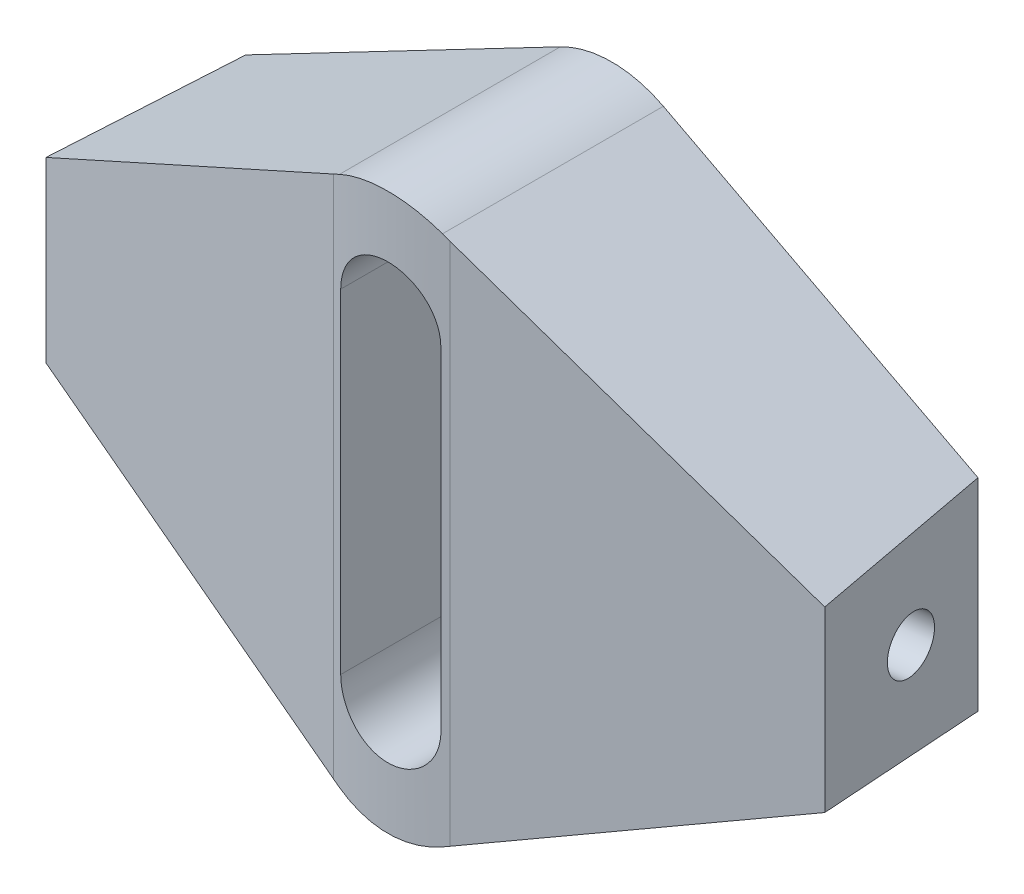
SolidWorks part; units mm, degrees
material "PVC hart"
ref_plane "Ebene vorne" through (0, 0, 0) normal (0, 0, 1) x (1, 0, 0)
ref_plane "Ebene oben" through (0, 0, 0) normal (0, 1, 0) x (1, 0, 0)
ref_plane "Ebene rechts" through (0, 0, 0) normal (1, 0, 0) x (0, 0, -1)
sketch "Skizze3" plane through (0, 0, 0) normal (0, 0, 1) x (1, 0, 0)
  line L0 (-17.5, 4) -> (-2.3149, 11.9318)
  line L1 (0, -7.5) -> (0, 7.5) construction
  line L2 (-2.25, -7.5) -> (-2.25, 7.5)
  line L3 (2.25, -7.5) -> (2.25, 7.5)
  line L4 (-17.5, 0) -> (17.5, 0) construction
  line L5 (-17.5, -4) -> (-2.3149, -11.9318)
  line L6 (0, 12.5) -> (0, -12.5) construction
  line L7 (17.5, -4) -> (2.3149, -11.9318)
  line L8 (-17.5, -4) -> (-17.5, 4)
  line L9 (17.5, 4) -> (2.3149, 11.9318)
  line L10 (17.5, -4) -> (17.5, 4)
  arc A0 (-2.25, -7.5) -> (2.25, -7.5) centre (0, -7.5) ccw
  arc A1 (2.25, 7.5) -> (-2.25, 7.5) centre (0, 7.5) ccw
  arc A2 (-2.3149, 11.9318) -> (2.3149, 11.9318) centre (0, 7.5) cw
  arc A3 (-2.3149, -11.9318) -> (2.3149, -11.9318) centre (0, -7.5) ccw
  point P4 (0, 0)
  point P15 (0, 0)
  dimension "D1" = 4.5
  dimension "D2" = 25
  dimension "D3" = 15
  dimension "D4" = 8
  dimension "D5" = 35
extrude "Aufsatz-Linear austragen3" add sketch "Skizze3" along normal blind 20 contours L2 A1 L3 | L8 | L2 | L3 | L10 | L3 A0 L2 region at (-9.7083, 7.5847, 0)
sketch "Skizze10" plane through (0, 0, 0) normal (0, 1, 0) x (1, 0, 0)
  line L0 (-16.4558, 0) -> (-17.5, -7.9316)
  line L1 (-17.5, 0) -> (-2.3149, 0) construction
  line L2 (-17.5, -20) -> (-17.5, 0) construction
  line L3 (-17.5, -7.9316) -> (-2.6105, -9.8918)
  line L5 (0, 0) -> (0, -20) construction
  line L6 (2.3149, 0) -> (-2.3149, 0) construction
  line L7 (-2.3149, -20) -> (2.3149, -20) construction
  line L8 (-16.4558, 0) -> (16.4558, 0)
  line L9 (16.4558, 0) -> (17.5, -7.9316)
  line L10 (17.5, -7.9316) -> (2.6105, -9.8918)
  arc A0 (-2.6105, -9.8918) -> (2.6105, -9.8918) centre (0, 9.9371) ccw
  dimension "D3" = 20
  dimension "D1" = 8
  dimension "D2" = 165
extrude "Schnitt-Linear austragen9" cut sketch "Skizze10" against normal through all and the other way through all flip side to cut
sketch "Skizze7" plane through (-17.1964, 0, 5.6253) normal (-0.9914, 0, -0.1305) x (-0.1305, 0, 0.9914)
  line L1 (-5.6739, 0) -> (2.3261, 0) construction
  line L2 (-5.6739, 4.5454) -> (-5.6739, -4.5454) construction
  line L3 (2.3261, -4) -> (2.3261, 4) construction
  circle A0 centre (-2.1739, 0) radius 1.23
  dimension "D1" = 2.46
  dimension "D2" = 4.5
  dimension "D3" = 3.5
extrude "Schnitt-Linear austragen8" cut sketch "Skizze7" against normal blind 12
mirror "Spiegeln4" about plane through (0, 0, 0) normal (1, 0, 0) of "Schnitt-Linear austragen8"
ref_axis "Bewegungsachse" through (0, -11.6078, 0) along (0, 1, 0)
